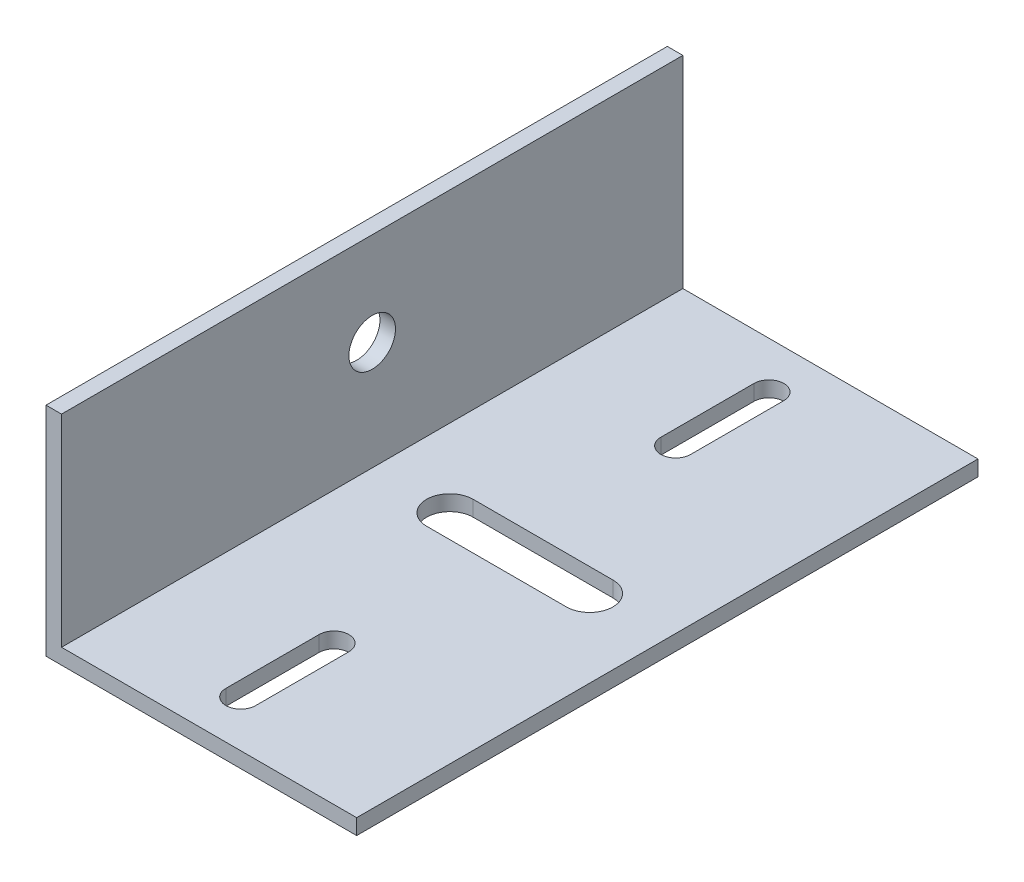
SolidWorks part; units mm, degrees
ref_plane "Спереди" through (0, 0, 0) normal (0, 0, 1) x (1, 0, 0)
ref_plane "Сверху" through (0, 0, 0) normal (0, 1, 0) x (1, 0, 0)
ref_plane "Справа" through (0, 0, 0) normal (1, 0, 0) x (0, 0, -1)
sketch "Эскиз2" plane through (0, 0, 0) normal (0, 0, 1) x (1, 0, 0)
  line L0 (0, 28) -> (0, 0)
  line L1 (0, 0) -> (40, 0)
extrude "Вытянуть-Тонкостенный1" add sketch "Эскиз2" along normal blind 80 thin thin type one direction reverse wall 2
sketch "Эскиз3" plane through (0, 2, 0) normal (0, 1, 0) x (1, 0, 0)
  line L0 (30, -37) -> (12, -37)
  line L1 (30, -43) -> (12, -43)
  line L2 (17.16, -6) -> (17.16, -18)
  line L3 (21, -6) -> (21, -18)
  line L4 (40, -40) -> (2, -40) construction
  line L5 (40, -80) -> (40, 0) construction
  line L6 (2, -80) -> (2, 0) construction
  line L7 (21, -74) -> (21, -62)
  line L8 (17.16, -74) -> (17.16, -62)
  arc A0 (30, -37) -> (30, -43) centre (30, -40) cw
  arc A1 (12, -37) -> (12, -43) centre (12, -40) ccw
  arc A2 (17.16, -6) -> (21, -6) centre (19.08, -6) cw
  arc A3 (17.16, -18) -> (21, -18) centre (19.08, -18) ccw
  arc A4 (17.16, -62) -> (21, -62) centre (19.08, -62) cw
  arc A5 (17.16, -74) -> (21, -74) centre (19.08, -74) ccw
extrude "Вырез-Вытянуть1" cut sketch "Эскиз3" against normal blind 10
sketch "Эскиз4" plane through (0, 0, 0) normal (-1, 0, 0) x (0, 0, 1)
  circle A0 centre (40, 16) radius 3
extrude "Вырез-Вытянуть2" cut sketch "Эскиз4" against normal blind 10
